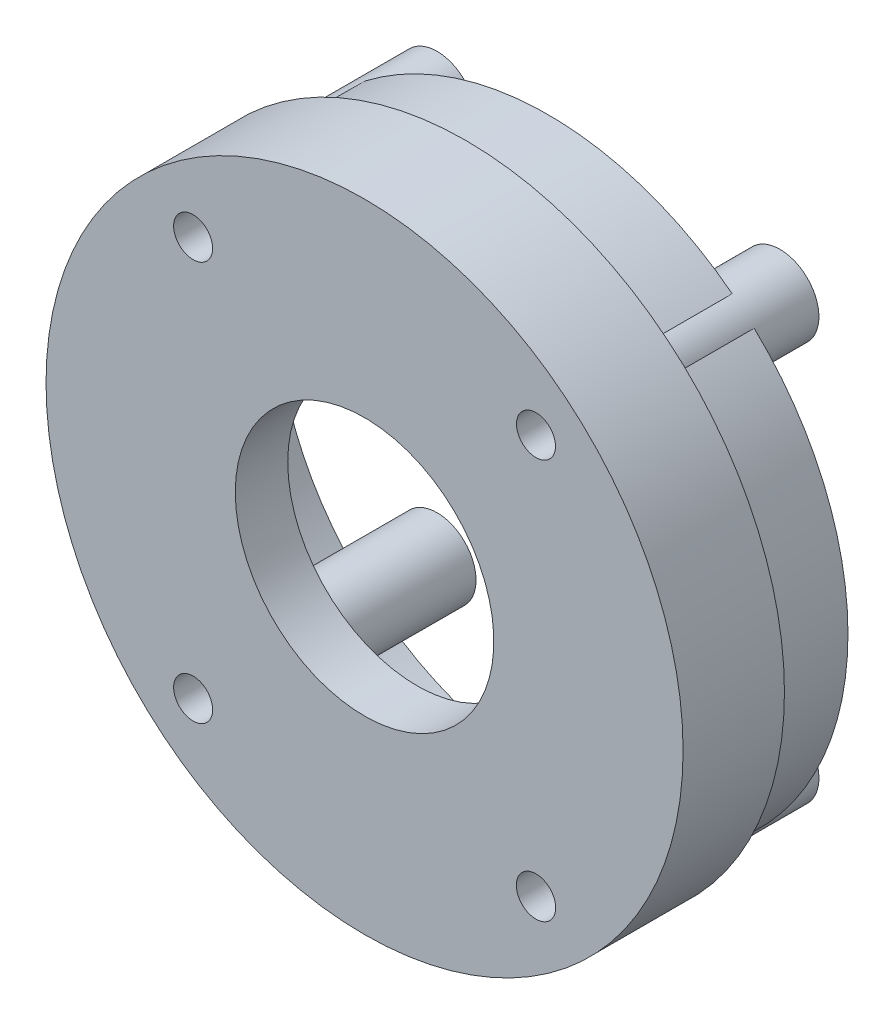
SolidWorks part; units mm, degrees
material "Cast Alloy Steel"
ref_plane "Front Plane" through (0, 0, 0) normal (0, 0, 1) x (1, 0, 0)
ref_plane "Top Plane" through (0, 0, 0) normal (0, 1, 0) x (1, 0, 0)
ref_plane "Right Plane" through (0, 0, 0) normal (1, 0, 0) x (0, 0, -1)
sketch "Sketch1" plane through (0, 0, 0) normal (0, 0, 1) x (1, 0, 0)
  circle A1 centre (0, 0) radius 17
  dimension "16" = 34
extrude "Boss-Extrude2" add sketch "Sketch1" along normal mid plane 5.41 contours A1
ref_plane "Plane4" through (0, 0, -2.705) normal (0, 0, -1) x (-1, 0, 0)
sketch "Sketch6" plane through (0, 0, -2.705) normal (0, 0, -1) x (-1, 0, 0)
  line L0 (9.15, -10.6621) -> (-9.15, -10.6621) construction
  line L1 (9.15, 10.6621) -> (9.15, -10.6621) construction
  line L2 (-14.05, 0) -> (14.05, 0) construction
  line L3 (12.1, -0.595) -> (12.1, 0.595) construction
  line L4 (14.4878, 0.595) -> (12.1, 0.595)
  line L5 (12.1, 0.595) -> (12.1, -0.595)
  line L6 (12.1, -0.595) -> (14.4878, -0.595)
  line L7 (14.05, 0) -> (16, 0) construction
  line L8 (0, -6.9) -> (0, 6.9) construction
  line L9 (-12.1, 0.595) -> (-12.1, -0.595)
  line L10 (-12.1, -0.595) -> (-14.4878, -0.595)
  line L11 (-14.4878, 0.595) -> (-12.1, 0.595)
  circle A2 centre (0, 0) radius 8.14
  circle A3 centre (0, 0) radius 6.9
  circle A5 centre (0, 0) radius 14.05 construction
  circle A8 centre (9.15, -10.6621) radius 2.08
  arc A13 (-10.9938, 11.6248) -> (-10.9938, -11.6248) centre (0, 0) ccw
  circle A16 centre (9.15, -10.6621) radius 1.04
  arc A18 (9.8218, 12.6306) -> (-9.8218, 12.6306) centre (0, 0) ccw
  arc A19 (-10.9091, 9.5521) -> (-10.9091, -9.5521) centre (0, 0) ccw
  arc A20 (7.7859, 12.2323) -> (-7.7859, 12.2323) centre (0, 0) ccw
  arc A21 (10.9091, -9.5521) -> (10.9091, 9.5521) centre (0, 0) ccw
  arc A22 (-7.7859, -12.2323) -> (7.7859, -12.2323) centre (0, 0) ccw
  circle A27 centre (-9.15, -10.6621) radius 2.08
  circle A28 centre (-9.15, -10.6621) radius 1.049
  circle A30 centre (9.15, 10.6621) radius 2.08
  circle A31 centre (9.15, 10.6621) radius 1.04
  circle A33 centre (-9.15, 10.6621) radius 2.08
  circle A34 centre (-9.15, 10.6621) radius 1.04
  arc A36 (-9.8218, -12.6306) -> (9.8218, -12.6306) centre (0, 0) ccw
  arc A37 (10.9938, -11.6248) -> (10.9938, 11.6248) centre (0, 0) ccw
  point P20 (0, 0)
  point P37 (12.1, 0)
  point P49 (-12.1, 0)
  dimension "D1" = 1.5
  dimension "D2" = 1.24
  dimension "D3" = 3.9
extrude "Boss-Extrude3" add sketch "Sketch6" along normal blind 4.39 contours A33 A20 A30 A18 | A8 A37 A30 A21 | A27 A36 A8 A22 | A33 A13 A27 A19 | L11 A19 L10 L9 | L6 A21 L4 L5 region at (-13.298, 0, -2.705) region at (-13.6861, 5.4681, -2.705) region at (0, 14.7, -2.705) region at (-8.7123, -12.8997, -2.705) region at (13.6861, 5.4681, -2.705) region at (13.298, 0, -2.705)
extrude "Cut-Extrude2" cut sketch "Sketch6<3>" against normal through all both and the other way through all contours A3 region at (0, 0, -2.705)
sketch "Sketch6<3>" plane through (0, 0, -2.705) normal (0, 0, -1) x (-1, 0, 0) same geometry as "Sketch6"
extrude "Cut-Extrude3" cut sketch "Sketch6<6>" against normal blind 4.11 contours A33 A19 A27 A22 A8 A21 A30 A20 A2 region at (-13.2939, 1.0049, -2.705)
sketch "Sketch6<6>" plane through (0, 0, -2.705) normal (0, 0, -1) x (-1, 0, 0) same geometry as "Sketch6"
extrude "Cut-Extrude4" cut sketch "Sketch6<7>" against normal blind 2.61 contours A2 A3 region at (7.9098, 0, -2.705)
sketch "Sketch6<7>" plane through (0, 0, -2.705) normal (0, 0, -1) x (-1, 0, 0) same geometry as "Sketch6"
extrude "Cut-Extrude5" cut sketch "Sketch6<12>" against normal through all contours A28 | A16 | A31 | A34 region at (-9.15, -10.6621, -2.705) region at (9.15, -10.6621, -2.705) region at (-9.15, 10.6621, -2.705)
sketch "Sketch6<12>" plane through (0, 0, -2.705) normal (0, 0, -1) x (-1, 0, 0) same geometry as "Sketch6"
extrude "Boss-Extrude4" add sketch "Sketch6<13>" along normal blind 7.61 contours A33 A34 | A30 A31 | A8 A16 | A27 A28 region at (-7.8337, 9.1283, -2.705) region at (-11.0916, -10.1007, -2.705) region at (7.311, 11.5005, -2.705) region at (8.762, -12.6457, -2.705)
sketch "Sketch6<13>" plane through (0, 0, -2.705) normal (0, 0, -1) x (-1, 0, 0) same geometry as "Sketch6"
ref_plane "Plane5" through (0, 0, 2.705) normal (0, 0, 1) x (1, 0, 0)
sketch "Sketch7" plane through (0, 0, 2.705) normal (0, 0, 1) x (1, 0, 0)
  circle A0 centre (9.15, -10.6621) radius 1.049 construction
  circle A1 centre (9.15, 10.6621) radius 1.04 construction
  circle A2 centre (-9.15, -10.6621) radius 1.04 construction
  circle A3 centre (-9.15, 10.6621) radius 1.04 construction
  circle A4 centre (9.15, -10.6621) radius 1.049
  circle A5 centre (9.15, 10.6621) radius 1.04
  circle A6 centre (-9.15, -10.6621) radius 1.04
  circle A7 centre (-9.15, 10.6621) radius 1.04
  circle A8 centre (-9.15, 10.6621) radius 1.75
  circle A9 centre (9.15, 10.6621) radius 1.75
  circle A10 centre (-9.15, -10.6621) radius 1.75
  circle A11 centre (9.15, -10.6621) radius 1.75
  dimension "D1" = 3.5
  dimension "D2" = 3.5
  dimension "D3" = 3.5
  dimension "D4" = 3.5
equation "\"Module\"= 1"
equation "\"Numer of theeth\"= 46"
equation "\"pressure angle\"= 20deg"
